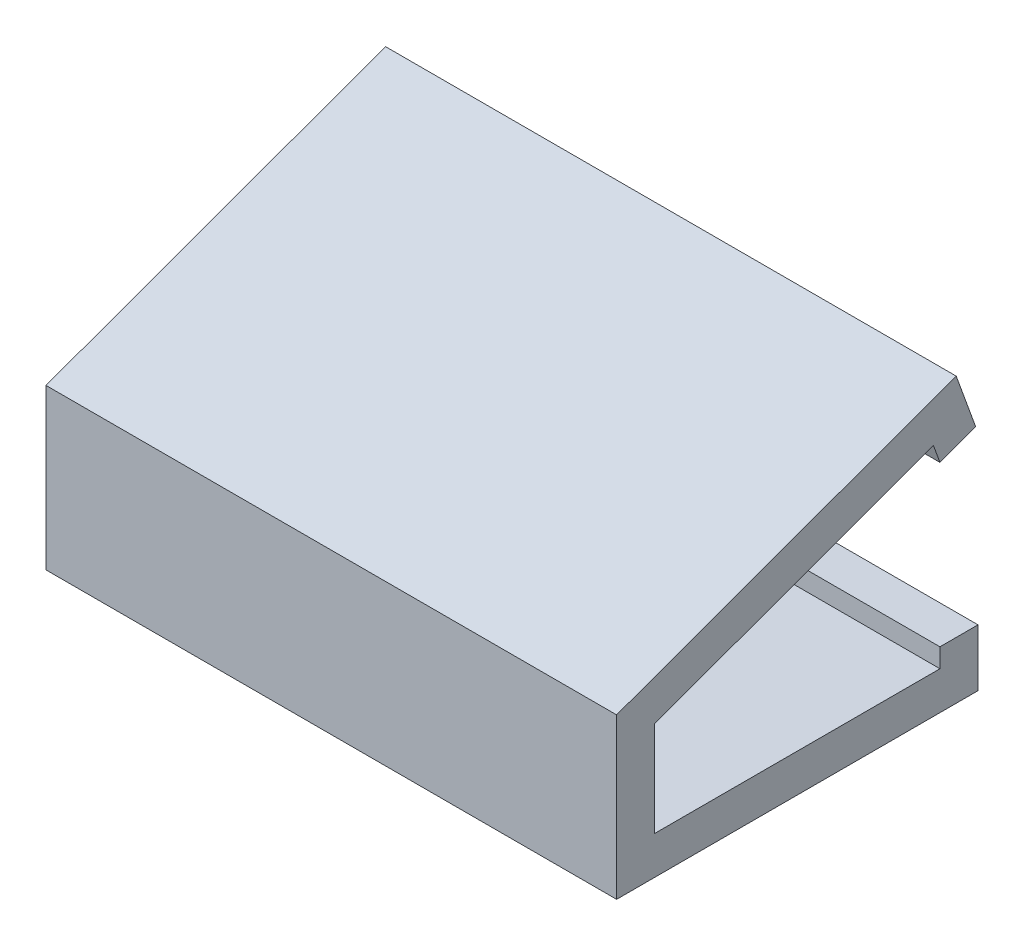
SolidWorks part; units mm, degrees
ref_plane "Front Plane" through (0, 0, 0) normal (0, 0, 1) x (1, 0, 0)
ref_plane "Top Plane" through (0, 0, 0) normal (0, 1, 0) x (1, 0, 0)
ref_plane "Right Plane" through (0, 0, 0) normal (1, 0, 0) x (0, 0, -1)
sketch "Sketch2" plane through (0, 0, 0) normal (1, 0, 0) x (0, 0, -1)
  line L0 (53.9074, -0.4008) -> (53.9074, -15.4008)
  line L1 (53.9074, -15.4008) -> (-41.0926, -15.4008)
  line L2 (-41.0926, -15.4008) -> (-41.0926, 26.6012)
  line L3 (-41.0926, 26.6012) -> (48.174, 59.0916)
  line L4 (48.174, 59.0916) -> (53.3043, 44.9962)
  line L5 (53.3043, 44.9962) -> (43.9074, 41.576)
  line L6 (43.9074, 41.576) -> (42.1973, 46.2745)
  line L7 (42.1973, 46.2745) -> (-31.0926, 19.5992)
  line L8 (-31.0926, 19.5992) -> (-31.0926, -5.4008)
  line L9 (-31.0926, -5.4008) -> (43.9074, -5.4008)
  line L10 (43.9074, -5.4008) -> (43.9074, -0.4008)
  line L11 (43.9074, -0.4008) -> (53.9074, -0.4008)
  line L12 (-31.0926, 19.5992) -> (38.8822, 19.5992) construction
  line L13 (-41.0926, 5.6002) -> (-31.0926, 5.6002) construction
  line L14 (3.5407, 42.8464) -> (6.9609, 33.4495) construction
  line L15 (6.4074, -5.4008) -> (6.4074, -15.4008) construction
  dimension "D1" = 20
  dimension "D2" = 25
  dimension "D7" = 75
  dimension "D3" = 10
  dimension "D4" = 5
extrude "MainBody" add sketch "Sketch2" along normal blind 150
equation "\"WedgeInnerHeight\"=25"
equation "\"D2@Sketch2\"=\"WedgeInnerHeight\""
equation "\"WedgeThickness\"=10"
equation "\"D3@Sketch2\"=\"WedgeThickness\""
equation "\"RetainingLip\"=5"
equation "\"D4@Sketch2\"=\"RetainingLip\""
equation "\"WedgeLength\"= 150"
equation "\"D1@MainBody\" = \"WedgeLength\""
equation "\"WedgeDepth\"= 75"
equation "\"D7@Sketch2\"=\"WedgeDepth\""
